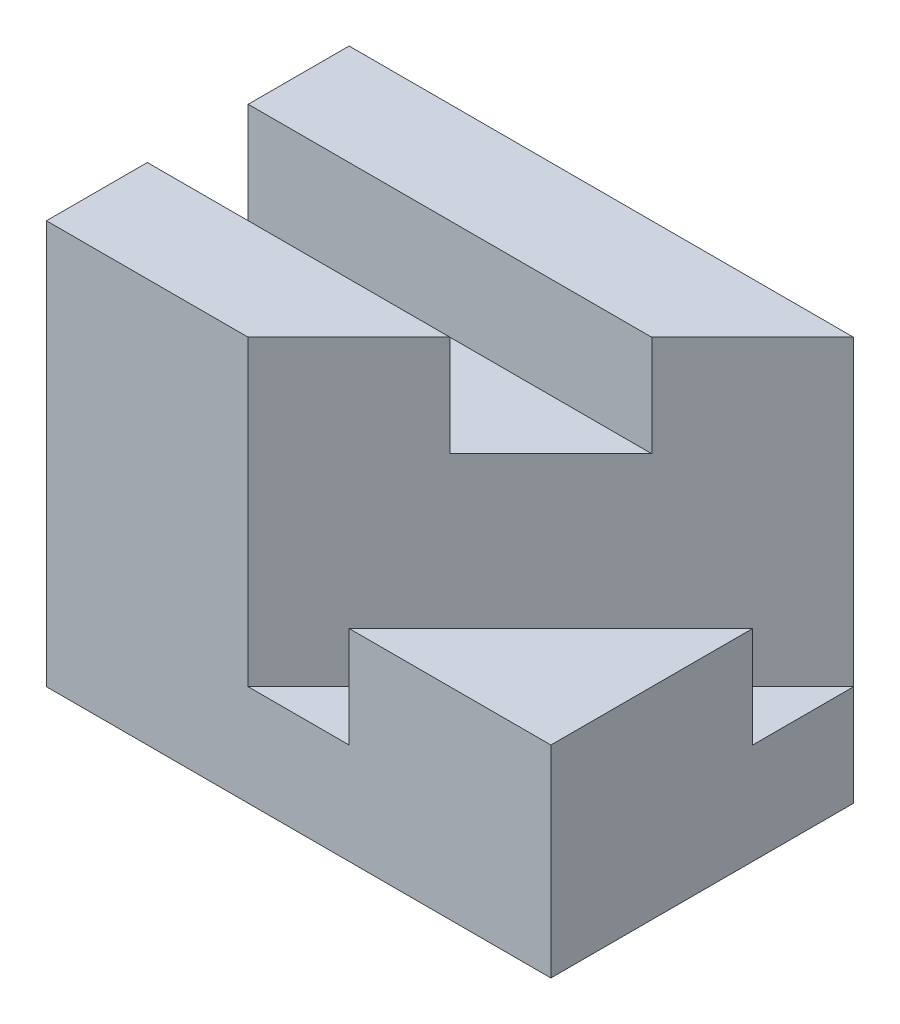
SolidWorks part; units mm, degrees
ref_plane "Front Plane" through (0, 0, 0) normal (0, 0, 1) x (1, 0, 0)
ref_plane "Top Plane" through (0, 0, 0) normal (0, 1, 0) x (1, 0, 0)
ref_plane "Right Plane" through (0, 0, 0) normal (1, 0, 0) x (0, 0, -1)
sketch "Sketch1" plane through (0, 0, 0) normal (0, 1, 0) x (1, 0, 0)
  line L0 (0, 0) -> (0, 30)
  line L1 (0, 30) -> (50, 30)
  line L2 (50, 30) -> (50, 0)
  line L3 (50, 0) -> (0, 0)
  line L4 (50, 30) -> (20, 0)
  line L5 (50, 20) -> (30, 0)
  line L6 (0, 10) -> (30, 10)
  line L7 (0, 20) -> (40, 20)
  dimension "D1" = 30
  dimension "D2" = 10
  dimension "D3" = 10
  dimension "D4" = 20
  dimension "D5" = 50
extrude "Boss-Extrude1" add sketch "Sketch1" along normal blind 10 contours L5 L2 L4 L3 region at (37.3333, 0, -12.6667)
extrude "Boss-Extrude2" add sketch "Sketch1<3>" along normal blind 20 contours L2 L5 L3 region at (43.3333, 0, -6.6667)
sketch "Sketch1<3>" plane through (0, 0, 0) normal (0, 1, 0) x (1, 0, 0) same geometry as "Sketch1"
extrude "Boss-Extrude3" add sketch "Sketch1<4>" along normal blind 30 contours L7 L0 L6 L4 region at (17.619, 0, -15.2381)
sketch "Sketch1<4>" plane through (0, 0, 0) normal (0, 1, 0) x (1, 0, 0) same geometry as "Sketch1"
extrude "Boss-Extrude4" add sketch "Sketch1<5>" along normal blind 40 contours L6 L0 L3 L4 | L0 L7 L4 L1 region at (12.6667, 0, -5.3333) region at (22.5926, 0, -25.1852)
sketch "Sketch1<5>" plane through (0, 0, 0) normal (0, 1, 0) x (1, 0, 0) same geometry as "Sketch1"
